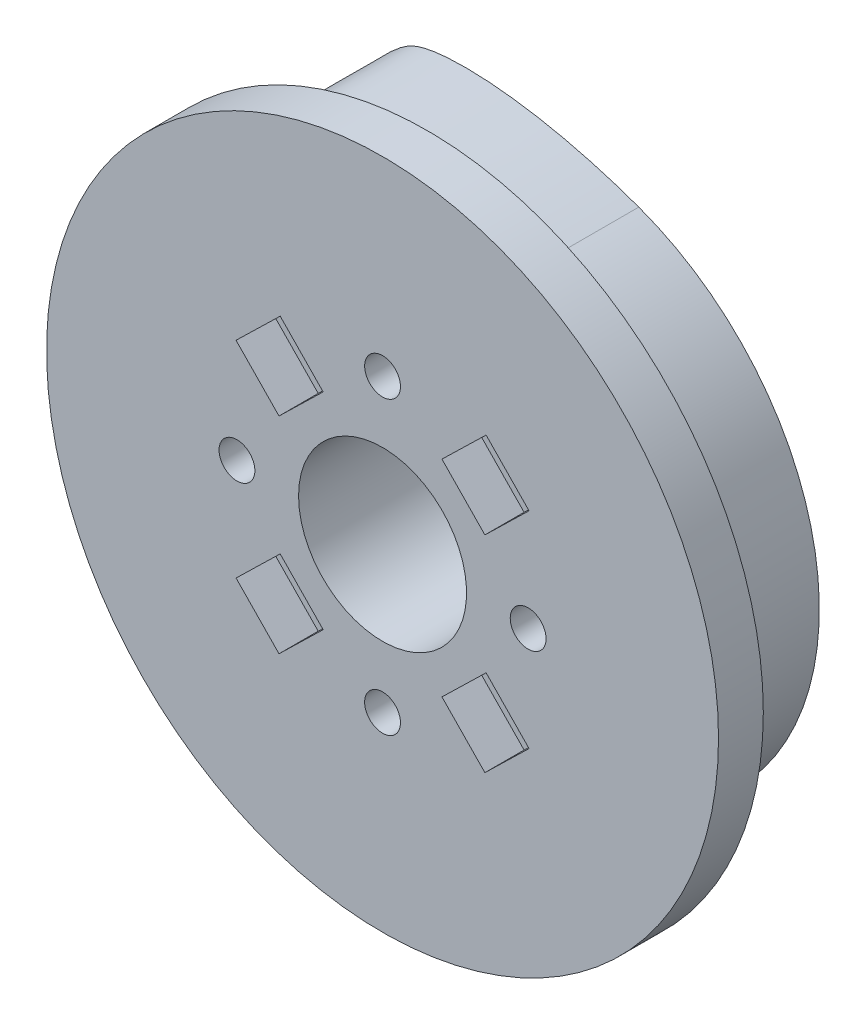
SolidWorks part; units mm, degrees
ref_plane "Front Plane" through (0, 0, 0) normal (1, 0, 0) x (0, 1, 0)
ref_plane "Top Plane" through (0, 0, 0) normal (0, 0, 1) x (0, 1, 0)
ref_plane "Right Plane" through (0, 0, 0) normal (0, 1, 0) x (-1, 0, 0)
sketch "Sketch1" plane through (0, 0, 0) normal (0, 0, 1) x (0, 1, 0)
  circle A0 centre (0, 0) radius 21
  circle A1 centre (0, 0) radius 13 construction
  circle A2 centre (0, 13) radius 1.6
  circle A3 centre (0, 13) radius 2.85
  circle A4 centre (13, 0) radius 2.85
  circle A5 centre (13, 0) radius 1.6
  circle A6 centre (0, -13) radius 2.85
  circle A7 centre (0, -13) radius 1.6
  circle A8 centre (-13, 0) radius 2.85
  circle A9 centre (-13, 0) radius 1.6
  point P19 (0, 0)
  dimension "D1" = 42
  dimension "D2" = 26
  dimension "D3" = 3.2
  dimension "D4" = 5.7
  dimension "D5" = 4
extrude "Boss-Extrude1" add sketch "Sketch1" along normal blind 10.5 contours A0 A8 A6 A4 A3 | A8 A9 | A3 A2 | A4 A5 | A6 A7 region at (0, 0, 0) region at (-13, -2.7694, 0) region at (0, 10.2306, 0) region at (13, -2.7694, 0) region at (0, -15.7694, 0)
sketch "Sketch2" plane through (0, 0, 0) normal (0, 0, -1) x (1, 0, 0)
  line L0 (0, 0) -> (0, 28) construction
  line L1 (0, 0) -> (-11.8333, -25.3766) construction
  line L2 (0, 0) -> (-26.3114, -9.5766) construction
  line L3 (0, 0) -> (9.5766, -26.3114) construction
  line L4 (-13.4939, -24.6023) -> (-49.7462, -7.6975) construction
  line L5 (-8.9203, -47.1248) -> (-49.9627, 65.6383) construction
  line L6 (47.1248, -8.9203) -> (-65.6383, -49.9627) construction
  circle A0 centre (0, 0) radius 28 construction
  circle A1 centre (0, 0) radius 24.5
  spline S0 degree 3 poles (-23.0225, -8.3795) (-19.9443, -16.8367) (-14.5106, -24.1678) (-9.1864, -26.6505) (-0.0777, -26.1007) (8.3795, -23.0225) knots 0 0 0 0 0.45 0.55 1 1 1 1
  circle M5 centre (0, 0) radius 21
  dimension "D1" = 56
  dimension "D2" = 49
  dimension "D6" = 20
  dimension "D7" = 30
  dimension "D8" = 30
  dimension "D3" = 205
  dimension "D4" = 45
  dimension "D5" = 45
  dimension "D9" = 90
  dimension "D10" = 90
  dimension "D11" = 90
extrude "Boss-Extrude3" add sketch "Sketch2" against normal up to surface (10.5 mm away) contours A1 M5 | A1 S0 region at (19.5016, 13.6552, 0) region at (-10.5348, 22.5834, 0) up to face at (21, 0, 10.5)
sketch "Sketch4" plane through (0, 0, 10.5) normal (0, 0, 1) x (1, 0, 0)
  circle A0 centre (0, 0) radius 30
  circle A5 centre (-13, 0) radius 1.6
  circle A6 centre (0, 13) radius 1.6
  circle A7 centre (13, 0) radius 1.6
  circle A8 centre (0, -13) radius 1.6
  dimension "D1" = 60
extrude "Boss-Extrude5" add sketch "Sketch4" along normal blind 4
sketch "Sketch3" plane through (0, 0, 0) normal (0, 0, -1) x (1, 0, 0)
  circle A0 centre (0, 0) radius 21
  circle A5 centre (-13, 0) radius 1.6
  circle A6 centre (0, 13) radius 1.6
  circle A7 centre (13, 0) radius 1.6
  circle A8 centre (0, -13) radius 1.6
  dimension "D1" = 42
extrude "Boss-Extrude4" add sketch "Sketch3" along normal blind 0.5
sketch "Sketch6" plane through (0, 0, -0.5) normal (0, 0, -1) x (1, 0, 0)
  line L0 (15.75, -2.75) -> (10.25, -2.75)
  line L1 (-2.75, 15.75) -> (2.75, 15.75)
  line L2 (-2.75, 15.75) -> (-2.75, 10.25)
  line L3 (-2.75, 10.25) -> (2.75, 10.25)
  line L4 (2.75, 15.75) -> (2.75, 10.25)
  line L5 (-2.75, 15.75) -> (2.75, 10.25) construction
  line L6 (-2.75, 10.25) -> (2.75, 15.75) construction
  line L7 (10.25, 2.75) -> (10.25, -2.75)
  line L8 (15.75, 2.75) -> (10.25, 2.75)
  line L9 (15.75, 2.75) -> (15.75, -2.75)
  line L10 (15.75, 2.75) -> (10.25, -2.75) construction
  line L11 (10.25, 2.75) -> (15.75, -2.75) construction
  line L12 (-2.75, -15.75) -> (-2.75, -10.25)
  line L13 (2.75, -10.25) -> (-2.75, -10.25)
  line L14 (2.75, -15.75) -> (2.75, -10.25)
  line L15 (2.75, -15.75) -> (-2.75, -15.75)
  line L16 (2.75, -15.75) -> (-2.75, -10.25) construction
  line L17 (2.75, -10.25) -> (-2.75, -15.75) construction
  line L18 (-15.75, 2.75) -> (-10.25, 2.75)
  line L19 (-10.25, -2.75) -> (-10.25, 2.75)
  line L20 (-15.75, -2.75) -> (-10.25, -2.75)
  line L21 (-15.75, -2.75) -> (-15.75, 2.75)
  line L22 (-15.75, -2.75) -> (-10.25, 2.75) construction
  line L23 (-10.25, -2.75) -> (-15.75, 2.75) construction
  point P0 (0, 13)
  point P21 (0, 0)
  dimension "D1" = 5.5
  dimension "D2" = 5.5
extrude "Cut-Extrude2" cut sketch "Sketch6" against normal offset from surface (3.5 mm away) 11.5 up to face at (14.6, 0, 14.5)
sketch "Sketch7" plane through (0, 0, 14.5) normal (0, 0, 1) x (1, 0, 0)
  line L0 (0, 0) -> (9.1924, 9.1924) construction
  line L1 (9.2456, 13.0807) -> (5.3041, 9.2465)
  line L2 (9.2456, 13.0807) -> (13.0807, 9.1383)
  line L3 (5.3041, 9.2465) -> (9.1392, 5.3041)
  line L4 (13.0807, 9.1383) -> (9.1392, 5.3041)
  line L5 (9.2456, 13.0807) -> (9.1392, 5.3041) construction
  line L6 (5.3041, 9.2465) -> (13.0807, 9.1383) construction
  line L7 (9.1383, -13.0807) -> (5.3041, -9.1392)
  line L8 (9.2465, -5.3041) -> (5.3041, -9.1392)
  line L9 (13.0807, -9.2456) -> (9.2465, -5.3041)
  line L10 (13.0807, -9.2456) -> (9.1383, -13.0807)
  line L11 (13.0807, -9.2456) -> (5.3041, -9.1392) construction
  line L12 (9.2465, -5.3041) -> (9.1383, -13.0807) construction
  line L13 (-13.0807, -9.1383) -> (-9.1392, -5.3041)
  line L14 (-5.3041, -9.2465) -> (-9.1392, -5.3041)
  line L15 (-9.2456, -13.0807) -> (-5.3041, -9.2465)
  line L16 (-9.2456, -13.0807) -> (-13.0807, -9.1383)
  line L17 (-9.2456, -13.0807) -> (-9.1392, -5.3041) construction
  line L18 (-5.3041, -9.2465) -> (-13.0807, -9.1383) construction
  line L19 (-9.1383, 13.0807) -> (-5.3041, 9.1392)
  line L20 (-9.2465, 5.3041) -> (-5.3041, 9.1392)
  line L21 (-13.0807, 9.2456) -> (-9.2465, 5.3041)
  line L22 (-13.0807, 9.2456) -> (-9.1383, 13.0807)
  line L23 (-13.0807, 9.2456) -> (-5.3041, 9.1392) construction
  line L24 (-9.2465, 5.3041) -> (-9.1383, 13.0807) construction
  circle A0 centre (0, 0) radius 13 construction
  circle A1 centre (9.1924, 9.1924) radius 1.6
  circle A10 centre (9.1924, -9.1924) radius 1.6
  circle A11 centre (-9.1924, -9.1924) radius 1.6
  circle A12 centre (-9.1924, 9.1924) radius 1.6
  point P18 (0, 0)
  point P34 (0, 0)
  dimension "D1" = 3.2
  dimension "D2" = 5.4988
  dimension "D3" = 5.5
extrude "Cut-Extrude3" cut sketch "Sketch7" against normal through all contours A1 | A12 | A11 | A10 region at (9.1924, 9.1924, 14.5) region at (9.1924, -9.1924, 14.5) region at (-9.1924, -9.1924, 14.5) region at (-9.1924, 9.1924, 14.5)
extrude "Cut-Extrude4" cut sketch "Sketch7<3>" against normal blind 3.5
sketch "Sketch7<3>" plane through (0, 0, 14.5) normal (0, 0, 1) x (1, 0, 0) same geometry as "Sketch7"
sketch "Sketch8" plane through (0, 0, -0.5) normal (0, 0, -1) x (1, 0, 0)
  circle A0 centre (0, 0) radius 7.5
  dimension "D1" = 15
extrude "Cut-Extrude5" cut sketch "Sketch8" against normal through all
